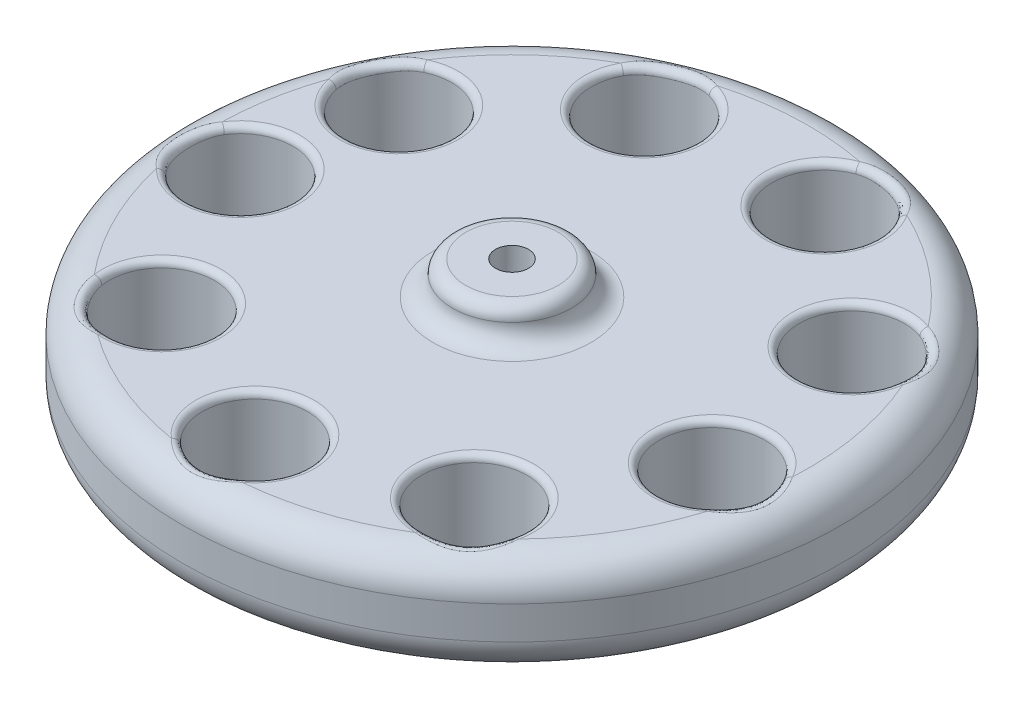
SolidWorks part; units mm, degrees
ref_plane "Front Plane" through (0, 0, 0) normal (0, 0, 1) x (1, 0, 0)
ref_plane "Top Plane" through (0, 0, 0) normal (0, 1, 0) x (1, 0, 0)
ref_plane "Right Plane" through (0, 0, 0) normal (1, 0, 0) x (0, 0, -1)
sketch "Sketch1" plane through (0, 0, 0) normal (0, 1, 0) x (1, 0, 0)
  circle A0 centre (0, 0) radius 50
extrude "Boss-Extrude1" add sketch "Sketch1" along normal blind 15
sketch "Sketch2" plane through (0, 0, 0) normal (0, 1, 0) x (1, 0, 0)
  circle A0 centre (-33.7445, 16.5801) radius 8
extrude "Cut-Extrude1" cut sketch "Sketch2" along normal blind 20
ref_axis "Axis1" through (0, 15.75, 0) along (0, -1, 0)
pattern_circular "CirPattern1" count 9 every 41 about axis through (0, 15.75, 0) along (0, -1, 0) of "Cut-Extrude1"
fillet "Fillet1" radius 5 2 edges at (0, 0, 50) (0, 15, 50)
ref_plane "Plane1" through (0, 15, 0) normal (0, 1, 0) x (1, 0, 0)
sketch "Sketch3" plane through (0, 15, 0) normal (0, 1, 0) x (1, 0, 0)
  circle A0 centre (0, 0) radius 9
extrude "Boss-Extrude2" add sketch "Sketch3" along normal blind 5
sketch "Sketch4" plane through (0, 0, 0) normal (0, 1, 0) x (1, 0, 0)
  circle A0 centre (0, 0) radius 2.5
extrude "Cut-Extrude2" cut sketch "Sketch4" against normal through all both and the other way through all
fillet "Fillet2" radius 3 1 edges at (0, 15, 9)
fillet "Fillet3" radius 2 1 edges at (0, 20, 9)
fillet "Fillet4" radius 1 34 edges at (-18.4832, 0.0312, -41.6403) (-41.2679, 0.0312, -19.3003) (-45.2247, 0.0312, 5.5011) (-30.5225, 0.0312, 33.8218) (-0.8465, 0.0312, 45.5502) (29.2448, 0.0312, 34.9325) (44.9891, 0.0312, 7.1776) (38.6627, 0.0312, -24.0985) (15.0343, 14.9688, -43.0059) (39.561, 14.9688, -22.5936) (44.6797, 14.9688, 8.9027) (27.8795, 14.9688, 36.0315) (-2.5979, 14.9688, 45.4839) (-31.8008, 14.9688, 32.6228) (-45.4029, 14.9688, 3.7575) (-16.8679, 14.9688, -42.3204) (-40.495, 14.9688, -20.8733) (-11.4854, 0, -27.2785) (-26.5644, 0, -13.0522) (-29.4445, 0, 3.0081) (-20.2486, 0, 21.5876) (-1.1191, 0, 29.5766) (18.5594, 0, 23.0559) (29.133, 0, 5.2244) (25.4145, 0, -15.1701) (9.2281, 15, -28.1224) (25.4145, 15, -15.1701) (29.133, 15, 5.2244) (18.5594, 15, 23.0559) (-1.1191, 15, 29.5766) (-20.2486, 15, 21.5876) (-29.4445, 15, 3.0081) (-11.4854, 15, -27.2785) (-26.5644, 15, -13.0522)
sketch "Sketch5" plane through (0, 0, 0) normal (0, 1, 0) x (1, 0, 0)
  circle A0 centre (0, 0) radius 6
extrude "Boss-Extrude3" add sketch "Sketch5" against normal blind 3
fillet "Fillet7" radius 2 1 edges at (0, -3, 6)
ref_plane "Plane2" through (0, 0, 0) normal (0, -1, 0) x (-1, 0, 0)
sketch "Sketch6" plane through (0, 0, 0) normal (0, -1, 0) x (-1, 0, 0)
  text T0 "1" font "Century Gothic" height in points 36
  text T1 "2" font "Century Gothic" height in points 36
  text T2 "3" font "Century Gothic" height in points 36
  text T3 "4" font "Century Gothic" height in points 36
  text T4 "5" font "Century Gothic" height in points 36
  text T5 "6" font "Century Gothic" height in points 36
  text T6 "7" font "Century Gothic" height in points 36
  text T7 "8" font "Century Gothic" height in points 36
  text T8 "9" font "Century Gothic" height in points 36
  point P9 (0, 0)
  point P10 (0, 0)
  point P11 (0, 0)
  point P12 (0, 0)
  point P13 (-24.057, 9.7301)
extrude "Cut-Extrude3" cut sketch "Sketch6" against normal blind 3
